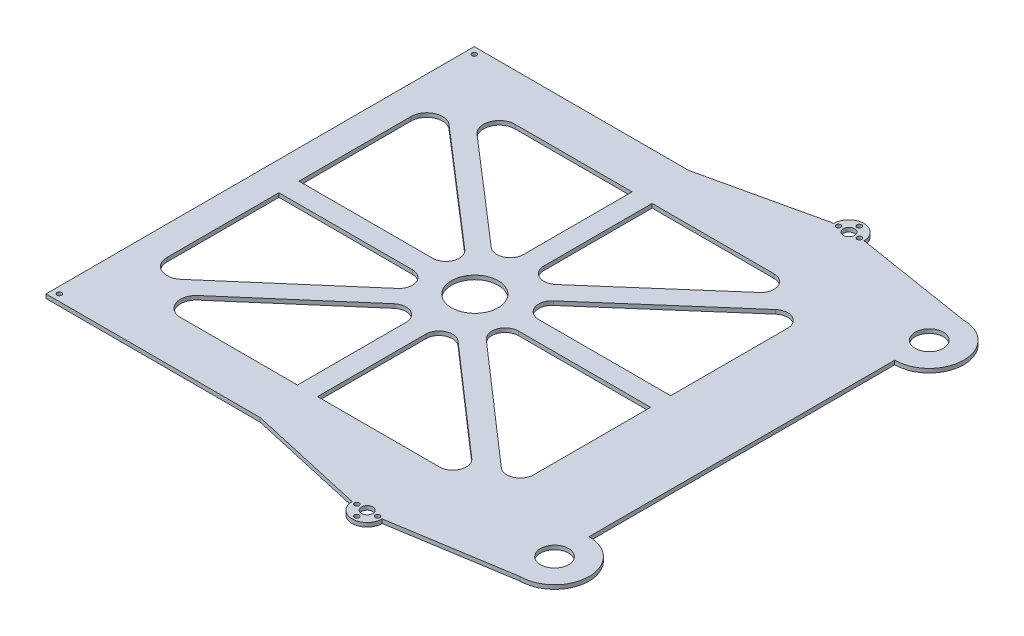
SolidWorks part; units mm, degrees
ref_plane "Front Plane" through (0, 0, 0) normal (0, 0, 1) x (1, 0, 0)
ref_plane "Top Plane" through (0, 0, 0) normal (0, 1, 0) x (1, 0, 0)
ref_plane "Right Plane" through (0, 0, 0) normal (1, 0, 0) x (0, 0, -1)
sketch "Sketch1" plane through (0, 0, 0) normal (0, 1, 0) x (1, 0, 0)
  line L0 (99.5709, 178.6008) -> (99.5709, 185.6008) construction
  line L1 (-160.4291, 154.3508) -> (-0.4291, 154.3508)
  line L2 (-160.4291, 154.3508) -> (-160.4291, -5.6492)
  line L3 (99.5709, 174.3508) -> (99.5709, -5.6492) construction
  line L4 (199.5709, 134.3508) -> (-155.4291, 134.3508) construction
  line L5 (110.8209, 174.3508) -> (103.8209, 174.3508) construction
  line L6 (95.3209, 174.3508) -> (88.3209, 174.3508) construction
  line L7 (199.5709, 221.375) -> (199.5709, -204.7205) construction
  line L8 (153.849, 134.3508) -> (0, 0) construction
  line L9 (0, 0) -> (-155.4291, 134.3508) construction
  line L10 (110.8209, 174.3508) -> (199.5709, 160.1508)
  line L11 (199.5709, -5.6492) -> (199.5709, 108.5508)
  line L12 (88.3209, 174.3508) -> (-0.4291, 154.3508)
  line L13 (153.849, 149.3508) -> (-155.4291, 149.3508) construction
  line L14 (-155.4291, 149.3508) -> (-155.4291, -160.6492) construction
  line L15 (199.5709, -5.6492) -> (140.3848, -5.6492)
  line L16 (153.849, -160.6492) -> (153.849, 149.3508) construction
  line L17 (98.6155, 119.3508) -> (7.5, 119.3508)
  line L18 (-102.6461, 98.6394) -> (-7.5, 16.3964)
  line L19 (7.5, 16.5067) -> (105.1931, 101.8186)
  line L20 (122.2714, 96.818) -> (13.5217, 1.8508)
  line L21 (138.849, 89.2858) -> (138.849, 1.8508)
  line L22 (17.8713, -5.6492) -> (-17.8713, -5.6492)
  line L23 (0, 0) -> (0, -84.1555) construction
  line L24 (-119.3473, 94.4377) -> (-12.2345, 1.8508)
  line L25 (-138.849, 85.5173) -> (-138.849, 1.8508)
  line L26 (-140.3848, -5.6492) -> (-160.4291, -5.6492)
  line L27 (-7.5, 16.3964) -> (-7.5, 119.3508)
  line L28 (7.5, 16.5067) -> (7.5, 119.3508)
  line L29 (-7.5, 119.3508) -> (-94.9354, 119.3508)
  line L30 (-140.3848, -5.6492) -> (-17.8713, -5.6492)
  line L31 (-138.849, 1.8508) -> (-12.2345, 1.8508)
  line L32 (13.5217, 1.8508) -> (138.849, 1.8508)
  line L33 (140.3848, -5.6492) -> (17.8713, -5.6492)
  circle A0 centre (99.5709, 174.3508) radius 4.25
  arc A1 (122.2714, 96.818) -> (138.849, 89.2858) centre (128.849, 89.2858) cw
  circle A2 centre (199.5709, 134.3508) radius 10.5
  arc A3 (98.6155, 119.3508) -> (105.1931, 101.8186) centre (98.6155, 109.3508) cw
  arc A5 (-94.9354, 119.3508) -> (-102.6461, 98.6394) centre (-94.9354, 107.5598) ccw
  arc A6 (199.5709, 160.1508) -> (199.5709, 108.5508) centre (199.5709, 134.3508) cw
  arc A7 (88.3209, 174.3508) -> (110.8209, 174.3508) centre (99.5709, 174.3508) cw
  circle A8 centre (-155.4291, 149.3508) radius 1.75
  arc A9 (-119.3473, 94.4377) -> (-138.849, 85.5173) centre (-127.058, 85.5173) ccw
  circle A10 centre (153.849, -160.6492) radius 1.75
  circle A11 centre (153.849, 149.3508) radius 1.75
  circle A12 centre (107.3209, 174.3508) radius 1.75
  circle A13 centre (91.8209, 174.3508) radius 1.75
  circle A14 centre (99.5709, 182.1008) radius 1.75
  point P47 (138.849, 111.2947)
  point P56 (-138.849, 111.2947)
  dimension "D5" = 21
  dimension "D6" = 8.5
  dimension "D7" = 360
  dimension "D8" = 15
  dimension "D10" = 25.8
  dimension "D12" = 3.5
  dimension "D19" = 7.5
  dimension "D9" = 3.5
  dimension "D16" = 10
  dimension "D2" = 180
  dimension "D3" = 140
  dimension "D4" = 5
  dimension "D11" = 15
  dimension "D13" = 15
  dimension "D14" = 7.5
  dimension "D15" = 7.5
  dimension "D17" = 15
  dimension "D18" = 5
  dimension "D20" = 7.5
extrude "Boss-Extrude2" add sketch "Sketch1" along normal blind 3
mirror "Mirror1" about plane through (199.5709, 3, 5.6492) normal (0, 0, -1) of "Boss-Extrude2"
fillet "Fillet1" radius 10 8 edges at (-12.2345, 1.5, 13.1492) (-12.2345, 1.5, -1.8508) (-7.5, 1.5, -16.3964) (7.5, 1.5, -16.5067) (13.5217, 1.5, -1.8508) (13.5217, 1.5, 13.1492) (7.5, 1.5, 27.805) (-7.5, 1.5, 27.6948)
sketch "Sketch2" plane through (0, 3, 0) normal (0, 1, 0) x (1, 0, 0)
  line L0 (199.5709, -5.6492) -> (-160.4291, -5.6492) construction
  line L1 (199.5709, 108.5508) -> (199.5709, -119.8492) construction
  line L2 (-160.4291, -165.6492) -> (-160.4291, 154.3508) construction
  circle A0 centre (0, -5.6492) radius 17.5
  dimension "D1" = 35
extrude "Cut-Extrude1" cut sketch "Sketch2" against normal blind 10
